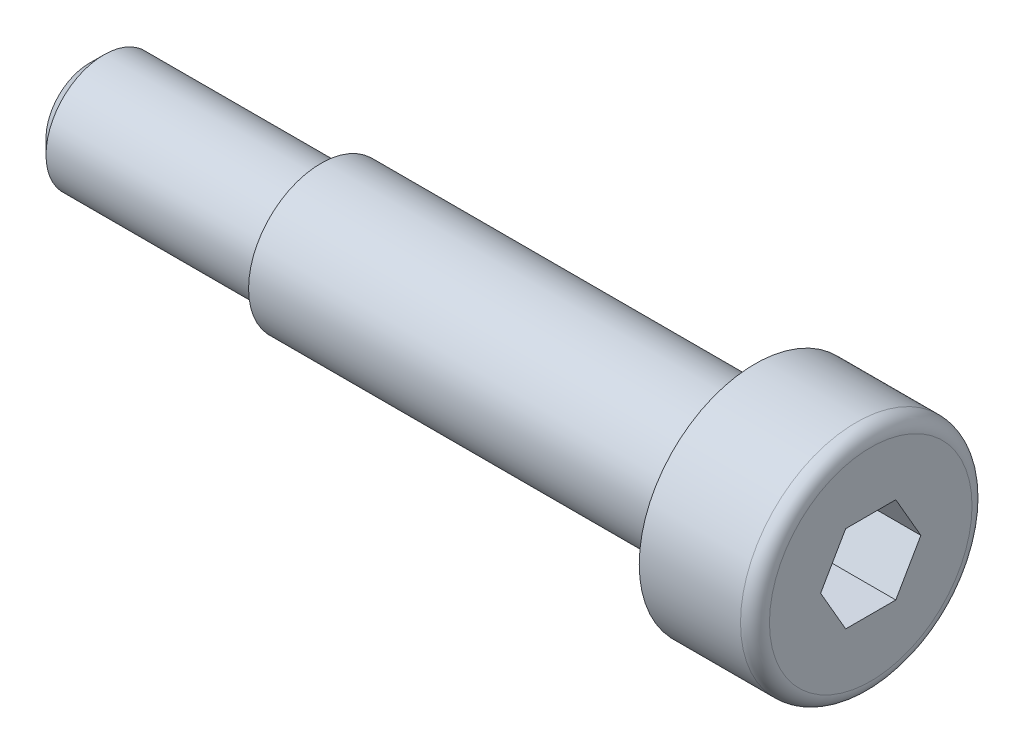
SolidWorks part; units mm, degrees
material "AISI 1020"
ref_plane "XY (Front)" through (0, 0, 0) normal (0, 0, 1) x (1, 0, 0)
ref_plane "XZ (Top)" through (0, 0, 0) normal (0, 1, 0) x (1, 0, 0)
ref_plane "YZ (Right)" through (0, 0, 0) normal (1, 0, 0) x (0, 0, -1)
ref_axis "X" through (-25.2, 0, 0) along (1, 0, 0)
ref_axis "Y" through (0, 5.5, 0) along (0, -1, 0)
ref_axis "Z" through (0, 0, -5.5) along (0, 0, 1)
sketch "Sketch1" plane through (0, 0, 0) normal (0, 0, 1) x (1, 0, 0)
  line L0 (0, 0) -> (0, 3.5)
  line L1 (-0.5, 4) -> (-4, 4)
  line L2 (-4, 4) -> (-4, 2.5)
  line L3 (-4, 2.5) -> (-19, 2.5)
  line L4 (-19, 2.5) -> (-19, 2)
  line L5 (-19, 2) -> (-27, 2)
  line L6 (-27, 2) -> (-27, 0)
  line L7 (-27, 0) -> (0, 0)
  line L8 (0, 0) -> (5.7531, 0) construction
  arc A0 (0, 3.5) -> (-0.5, 4) centre (-0.5, 3.5) ccw
  dimension "R" = 0.5
  dimension "d3" = 8
  dimension "d1" = 5
  dimension "M" = 4
  dimension "l3" = 4
  dimension "l1" = 15
  dimension "l2" = 8
revolve "Revolve1" add sketch "Sketch1" angle 360 about L8
chamfer "Chamfer1" distance 0.5 angle 45 1 edges at (-27, 0, 2)
sketch "Sketch2" plane through (0, 0, 0) normal (1, 0, 0) x (0, 0, -1)
  line L1 (1.7321, 0) -> (0.866, 1.5)
  line L2 (0.866, 1.5) -> (-0.866, 1.5)
  line L3 (-0.866, 1.5) -> (-1.7321, 0)
  line L4 (-1.7321, 0) -> (-0.866, -1.5)
  line L5 (-0.866, -1.5) -> (0.866, -1.5)
  line L6 (0.866, -1.5) -> (1.7321, 0)
  circle A0 centre (0, 0) radius 1.5 construction
  dimension "AF" = 3
extrude "Cut-Extrude1" cut sketch "Sketch2" against normal blind 2.4
